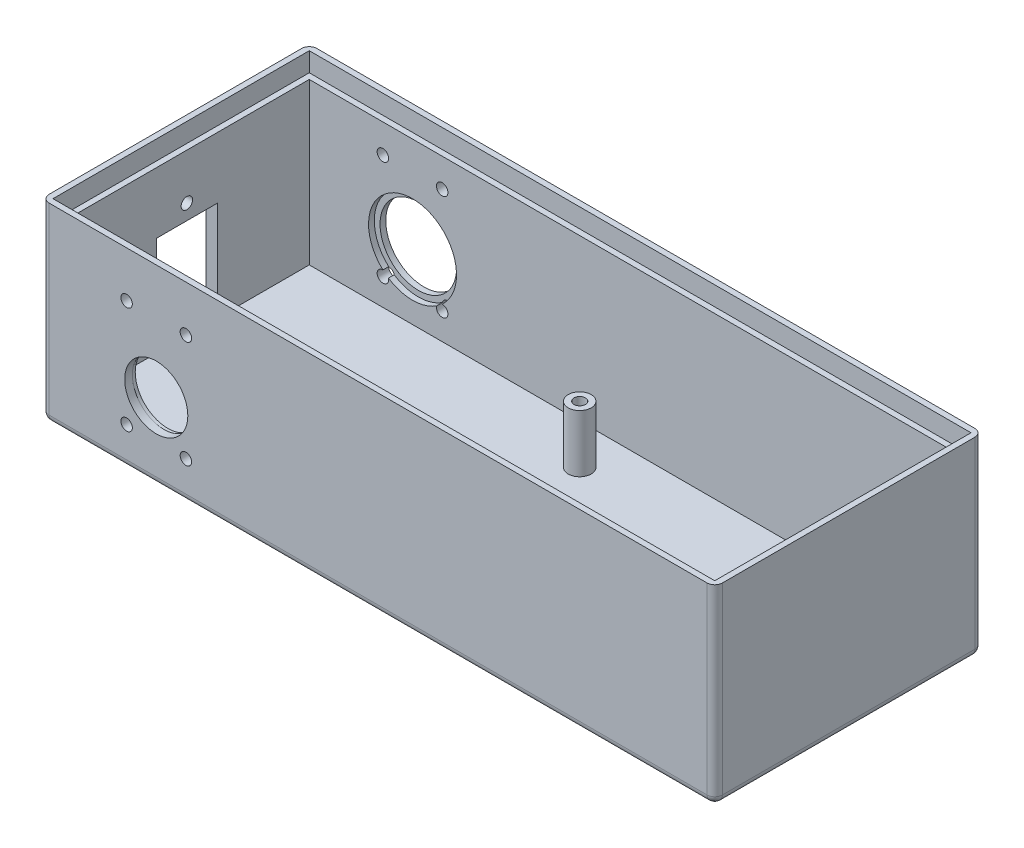
SolidWorks part; units mm, degrees
ref_plane "Front Plane" through (0, 0, 0) normal (0, 0, 1) x (1, 0, 0)
ref_plane "Top Plane" through (0, 0, 0) normal (0, 1, 0) x (1, 0, 0)
ref_plane "Right Plane" through (0, 0, 0) normal (1, 0, 0) x (0, 0, -1)
sketch "Sketch1" plane through (0, 0, 0) normal (0, 1, 0) x (1, 0, 0)
  line L1 (88, -35) -> (-88, -35)
  line L2 (88, -35) -> (88, 35)
  line L3 (88, 35) -> (-88, 35)
  line L4 (-88, -35) -> (-88, 35)
  line L5 (88, -35) -> (-88, 35) construction
  line L6 (88, 35) -> (-88, -35) construction
  point P0 (0, 0)
  dimension "D1" = 176
  dimension "D2" = 70
extrude "Boss-Extrude1" add sketch "Sketch1" along normal blind 50
sketch "Sketch2" plane through (0, 50, 0) normal (0, 1, 0) x (1, 0, 0)
  line L0 (-88, 35) -> (-88, -35) construction
  line L1 (85, -32) -> (-85, -32)
  line L2 (85, -32) -> (85, 32)
  line L3 (85, 32) -> (-85, 32)
  line L4 (-85, -32) -> (-85, 32)
  line L5 (85, -32) -> (-85, 32) construction
  line L6 (85, 32) -> (-85, -32) construction
  line L7 (88, 35) -> (-88, 35) construction
  point P0 (0, 0)
  dimension "D1" = 3
  dimension "D2" = 3
extrude "Cut-Extrude1" cut sketch "Sketch2" against normal blind 47
sketch "Sketch3" plane through (0, 50, 0) normal (0, 1, 0) x (1, 0, 0)
  line L0 (-88, 35) -> (-88, -35) construction
  line L1 (86.5, -33.5) -> (-86.5, -33.5)
  line L2 (86.5, -33.5) -> (86.5, 33.5)
  line L3 (86.5, 33.5) -> (-86.5, 33.5)
  line L4 (-86.5, -33.5) -> (-86.5, 33.5)
  line L5 (86.5, -33.5) -> (-86.5, 33.5) construction
  line L6 (86.5, 33.5) -> (-86.5, -33.5) construction
  line L7 (88, 35) -> (-88, 35) construction
  point P0 (0, 0)
  dimension "D1" = 1.5
  dimension "D2" = 1.5
extrude "Cut-Extrude2" cut sketch "Sketch3" against normal blind 5
sketch "Sketch4" plane through (0, 3, 0) normal (0, 1, 0) x (1, 0, 0)
  line L0 (85, -32) -> (85, 32) construction
  line L1 (-85, -32) -> (85, -32) construction
  line L3 (-3.8, 21.5) -> (71.2, 21.5) construction
  circle A0 centre (-4.8, -27) radius 3
  circle A1 centre (78, -27) radius 3
  circle A2 centre (71.2, 21.5) radius 3
  circle A3 centre (-3.8, 21.5) radius 3
  circle A4 centre (-4.8, -27) radius 1.5
  circle A5 centre (-3.8, 21.5) radius 1.5
  circle A6 centre (71.2, 21.5) radius 1.5
  circle A7 centre (78, -27) radius 1.5
  dimension "D1" = 6
  dimension "D7" = 3
  dimension "D2" = 82.8
  dimension "D3" = 48.5
  dimension "D4" = 75
  dimension "D5" = 7
  dimension "D6" = 5
  dimension "D8" = 1
extrude "Boss-Extrude2" add sketch "Sketch4" along normal blind 15
sketch "Sketch5" plane through (0, 0, -35) normal (0, 0, -1) x (-1, 0, 0)
  line L0 (-88, 0) -> (88, 0) construction
  line L1 (88, 50) -> (88, 0) construction
  line L2 (58, 20) -> (58, 59.0899) construction
  circle A0 centre (58, 20) radius 10
  circle A1 centre (65.75, 37.5) radius 1.5
  circle A2 centre (50.25, 37.5) radius 1.5
  circle A3 centre (50.25, 10) radius 1.5
  circle A4 centre (65.75, 10) radius 1.5
  dimension "D1" = 20
  dimension "D4" = 3
  dimension "D2" = 20
  dimension "D3" = 30
  dimension "D5" = 15.5
  dimension "D6" = 27.5
  dimension "D7" = 10
extrude "Cut-Extrude3" cut sketch "Sketch5" against normal up to next
sketch "Sketch6" plane through (0, 0, -32) normal (0, 0, 1) x (1, 0, 0)
  circle A0 centre (-58, 20) radius 11.5
  circle A1 centre (-58, 20) radius 10 construction
  dimension "D1" = 1.5
extrude "Cut-Extrude4" cut sketch "Sketch6" against normal blind 1.5
sketch "Sketch7" plane through (0, 0, 35) normal (0, 0, 1) x (1, 0, 0)
  line L0 (-88, 0) -> (88, 0) construction
  line L1 (-88, 50) -> (-88, 0) construction
  line L2 (-58, 20) -> (-58, 52.5143) construction
  circle A0 centre (-58, 20) radius 8.25
  circle A1 centre (-65.75, 38) radius 1.5
  circle A2 centre (-50.25, 38) radius 1.5
  circle A3 centre (-65.75, 10) radius 1.5
  circle A4 centre (-50.25, 10) radius 1.5
  point P14 (0, 0)
  point P15 (0, 0)
  dimension "D1" = 16.5
  dimension "D4" = 3
  dimension "D2" = 20
  dimension "D3" = 30
  dimension "D5" = 10
  dimension "D6" = 15.5
  dimension "D7" = 28
extrude "Cut-Extrude5" cut sketch "Sketch7" against normal up to next
sketch "Sketch8" plane through (0, 0, 32) normal (0, 0, -1) x (-1, 0, 0)
  circle A0 centre (58, 20) radius 8.5
  dimension "D1" = 17
extrude "Cut-Extrude6" cut sketch "Sketch8" against normal blind 1
fillet "Fillet1" radius 2 8 edges at (0, 0, 35) (-88, 25, 35) (-88, 0, 0) (-88, 25, -35) (88, 25, 35) (88, 0, 0) (0, 0, -35) (88, 25, -35)
sketch "Sketch9" plane through (-88, 0, 0) normal (-1, 0, 0) x (0, 0, 1)
  line L0 (-33, 2) -> (33, 2) construction
  line L1 (8, 8) -> (-8, 8)
  line L2 (8, 8) -> (8, 29)
  line L3 (8, 29) -> (-8, 29)
  line L4 (-8, 8) -> (-8, 29)
  line L5 (8, 8) -> (-8, 29) construction
  line L6 (8, 29) -> (-8, 8) construction
  circle A0 centre (0, 33) radius 1.5
  circle A1 centre (0, 6) radius 1
  point P0 (0, 18.5)
  point P9 (0, 0)
  point P10 (0, 0)
  point P11 (0, 0)
  dimension "D3" = 3
  dimension "D4" = 2
  dimension "D1" = 21
  dimension "D2" = 16
  dimension "D5" = 4
  dimension "D6" = 2
  dimension "D7" = 6
extrude "Cut-Extrude7" cut sketch "Sketch9" against normal up to next
